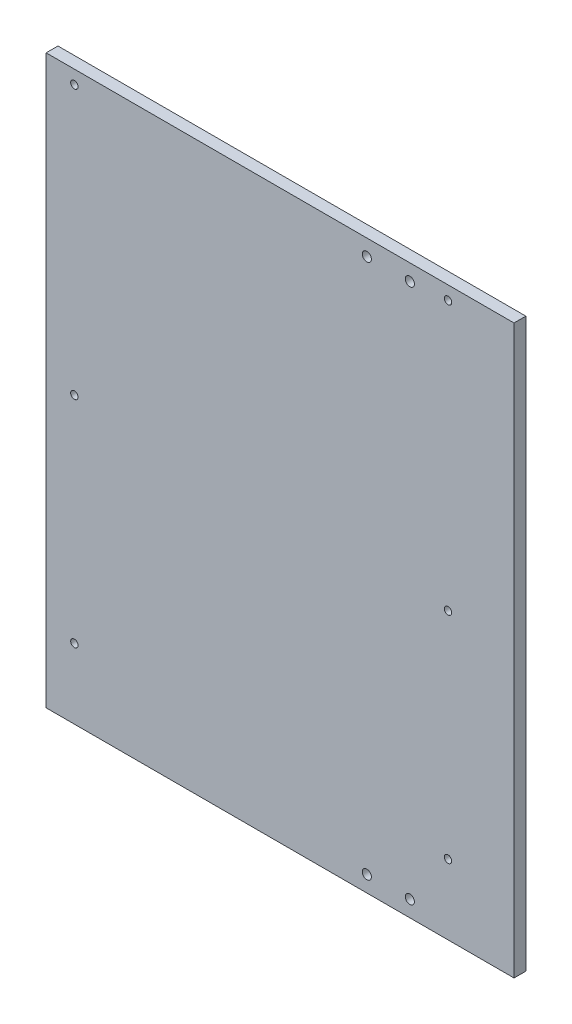
SolidWorks part; units mm, degrees
ref_plane "Front Plane" through (0, 0, 0) normal (0, 0, 1) x (1, 0, 0)
ref_plane "Top Plane" through (0, 0, 0) normal (0, 1, 0) x (1, 0, 0)
ref_plane "Right Plane" through (0, 0, 0) normal (1, 0, 0) x (0, 0, -1)
sketch "Sketch1" plane through (0, 0, 0) normal (0, 0, 1) x (1, 0, 0)
  line L1 (-129.267, -426.0852) -> (44.7972, -426.0852)
  line L2 (-129.267, -426.0852) -> (-129.267, -215.0378)
  line L3 (-129.267, -215.0378) -> (44.7972, -215.0378)
  line L4 (44.7972, -426.0852) -> (44.7972, -215.0378)
  line L6 (-129.267, -426.0852) -> (-129.267, -215.0378) construction
  line L8 (-114.9139, -409.7584) -> (-120.4139, -409.7584) construction
  line L9 (-119.735, -215.0378) -> (-114.9139, -215.0378) construction
extrude "Boss-Extrude1" add sketch "Sketch1" along normal blind 4.4
hole_wizard "Tap Drill for M3 Tap1" positions "Sketch3" profile "Sketch2" hole size "M3" standard "ISO" end condition through all
sketch "Sketch3" plane through (0, 0, 4.4) normal (0, 0, 1) x (1, 0, 0)
  point P0 (-118.767, -220.0378)
  point P2 (20.233, -220.0378)
  point P8 (-118.767, -320.0378)
  point P10 (20.233, -320.0378)
  point P12 (20.233, -400.0378)
  point P22 (-118.767, -400.0378)
sketch "Sketch2" plane through (-118.767, -220.0378, 4.4) normal (1, 0, 0) x (0, -1, 0)
  line L0 (0, 0) -> (0, 4.4)
  line L1 (0, 4.4) -> (1.375, 4.4)
  line L2 (1.375, 4.4) -> (1.375, 0)
  line L5 (1.375, 0) -> (0, 0)
  line L11 (0, -6.35) -> (0, 107.95) construction
  dimension "Thru Hole Dia." = 2.75
  dimension "Thru Hole Depth" = 4.4
hole_wizard "M3 Clearance Hole1" positions "Sketch5" profile "Sketch4" hole size "M3" standard "ISO" end condition through all
sketch "Sketch5" plane through (0, 0, 4.4) normal (0, 0, 1) x (1, 0, 0)
  point P0 (-9.9674, -420.0852)
  point P2 (6.0402, -420.0852)
  point P5 (-9.9674, -221.0378)
  point P7 (6.0402, -221.0378)
sketch "Sketch4" plane through (-9.9674, -420.0852, 4.4) normal (1, 0, 0) x (0, -1, 0)
  line L0 (0, 0) -> (0, 4.4)
  line L1 (0, 4.4) -> (1.7, 4.4)
  line L2 (1.7, 4.4) -> (1.7, 0)
  line L5 (1.7, 0) -> (0, 0)
  line L11 (0, -6.35) -> (0, 107.95) construction
  dimension "Thru Hole Dia." = 3.4
  dimension "Thru Hole Depth" = 4.4
sketch "Sketch6" plane through (0, 0, 8.6) normal (0, 0, 1) x (1, 0, 0)
  line L8 (-120.4884, -256.7906) -> (-120.4884, -416.7906)
  line L9 (-120.4884, -416.7906) -> (39.5116, -416.7906)
  line L10 (39.5116, -416.7906) -> (39.5116, -256.7906)
  line L11 (39.5116, -256.7906) -> (-120.4884, -256.7906)
extrude "Cut-Extrude1" [suppressed] cut sketch "Sketch6" against normal blind 31
sketch "Sketch7" plane through (0, 0, 4.4) normal (0, 0, 1) x (1, 0, 0)
  line L0 (-129.267, -215.0378) -> (-129.267, -426.0852) construction
  line L1 (-129.267, -215.0378) -> (-101.1846, -215.0378)
  line L2 (-129.267, -215.0378) -> (-129.267, -426.0852)
  line L3 (-129.267, -426.0852) -> (-101.1846, -426.0852)
  line L4 (-101.1846, -215.0378) -> (-101.1846, -426.0852)
  line L5 (-129.267, -426.0852) -> (44.7972, -426.0852) construction
extrude "Cut-Extrude2" [suppressed] cut sketch "Sketch7" against normal blind 2
